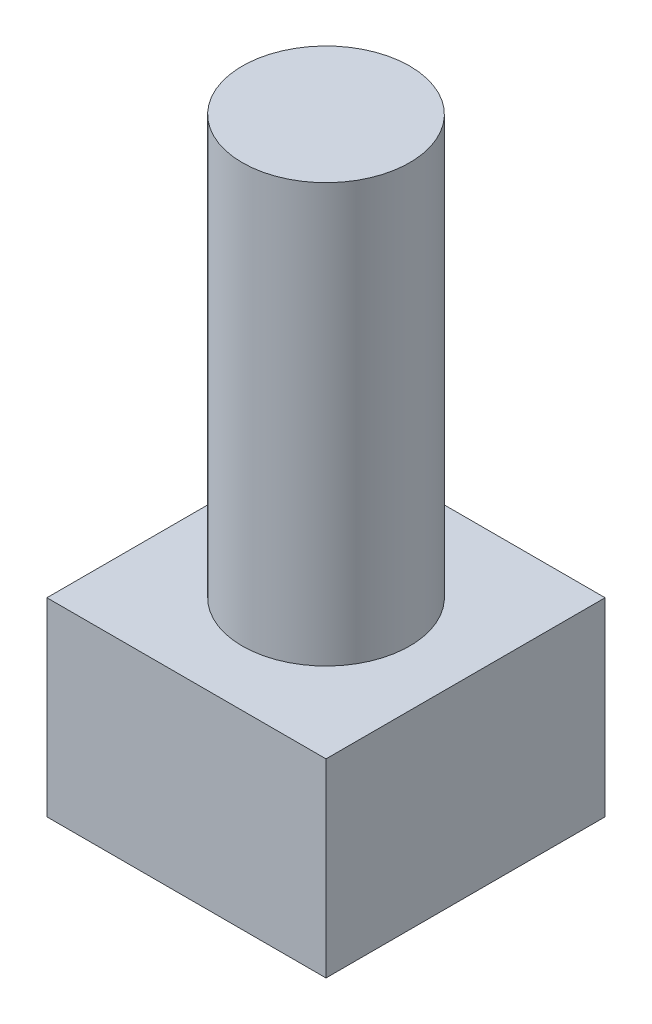
SolidWorks part; units mm, degrees
ref_plane "Front Plane" through (0, 0, 0) normal (0, 0, 1) x (1, 0, 0)
ref_plane "Top Plane" through (0, 0, 0) normal (0, 1, 0) x (1, 0, 0)
ref_plane "Right Plane" through (0, 0, 0) normal (1, 0, 0) x (0, 0, -1)
sketch "Sketch1" plane through (0, 0, 0) normal (0, 1, 0) x (1, 0, 0)
  line L1 (-5, 5) -> (5, 5)
  line L2 (-5, 5) -> (-5, -5)
  line L3 (-5, -5) -> (5, -5)
  line L4 (5, 5) -> (5, -5)
  line L5 (-5, 5) -> (5, -5) construction
  line L6 (-5, -5) -> (5, 5) construction
  point P0 (0, 0)
  dimension "D1" = 10
  dimension "D2" = 10
extrude "Boss-Extrude1" add sketch "Sketch1" along normal blind 6.8
sketch "Sketch2" plane through (0, 6.8, 0) normal (0, 1, 0) x (1, 0, 0)
  circle A0 centre (0, 0) radius 3
  dimension "D1" = 6
extrude "Boss-Extrude2" add sketch "Sketch2" along normal blind 15
sketch "Sketch3" plane through (0, 21.8, 0) normal (0, 1, 0) x (1, 0, 0)
  point P0 (0, 0)
